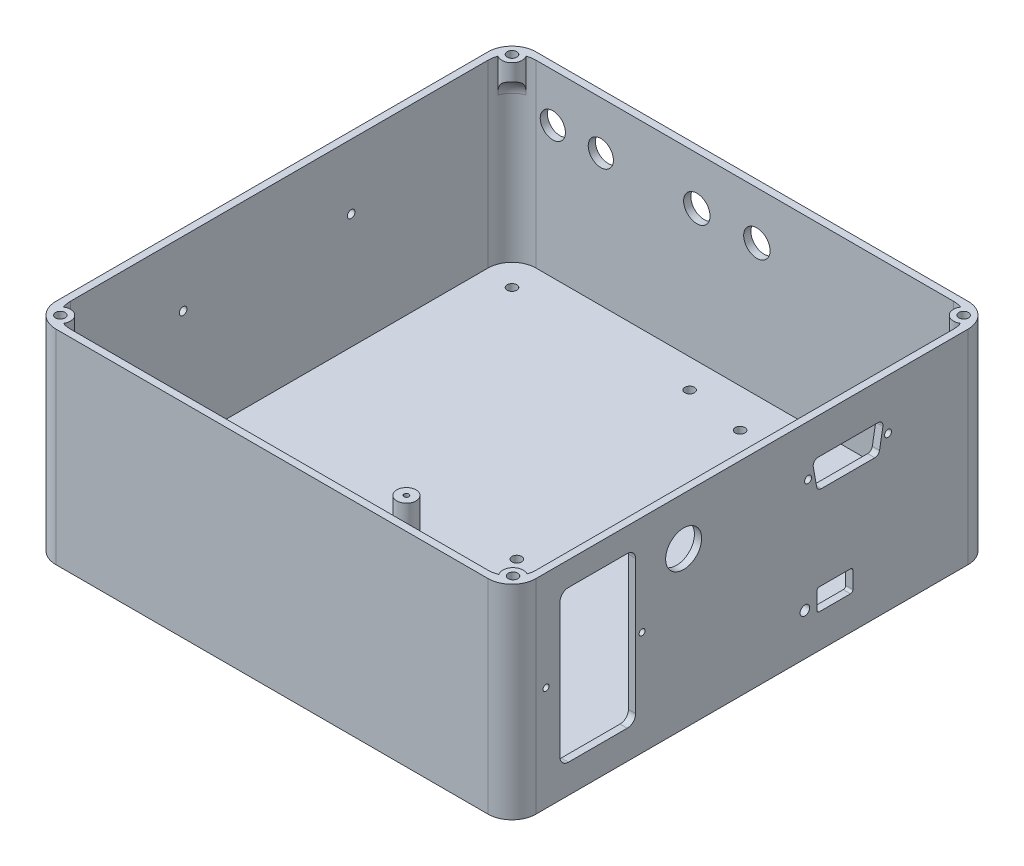
SolidWorks part; units mm, degrees
ref_plane "Front Plane" through (0, 0, 0) normal (0, 0, 1) x (1, 0, 0)
ref_plane "Top Plane" through (0, 0, 0) normal (0, 1, 0) x (1, 0, 0)
ref_plane "Right Plane" through (0, 0, 0) normal (1, 0, 0) x (0, 0, -1)
sketch "Sketch1" plane through (0, 0, 0) normal (0, 1, 0) x (1, 0, 0)
  line L1 (0, 0) -> (200, 0)
  line L2 (0, 0) -> (0, 200)
  line L3 (0, 200) -> (200, 200)
  line L4 (200, 0) -> (200, 200)
  dimension "D1" = 200
  dimension "D2" = 200
extrude "Boss-Extrude1" add sketch "Sketch1" along normal blind 4 and the other way blind 6
sketch "Sketch2" plane through (0, 4, 0) normal (0, 1, 0) x (1, 0, 0)
  line L1 (0, 0) -> (200, 0)
  line L2 (0, 0) -> (0, 200)
  line L3 (0, 200) -> (200, 200)
  line L4 (200, 0) -> (200, 200)
  line L5 (3, 3) -> (197, 3)
  line L6 (3, 3) -> (3, 197)
  line L7 (3, 197) -> (197, 197)
  line L8 (197, 3) -> (197, 197)
  dimension "D1" = 3
  dimension "D2" = 3
  dimension "D3" = 3
  dimension "D4" = 3
extrude "Boss-Extrude2" add sketch "Sketch2" along normal blind 75
sketch "Sketch3" plane through (200, 0, 0) normal (1, 0, 0) x (0, 0, -1)
  line L4 (200, 79) -> (200, -6) construction
  line L5 (156.65, 58.05) -> (123.35, 58.05) construction
  line L7 (0, 79) -> (200, 79) construction
  line L8 (140, 64) -> (140, 52.1) construction
  line L9 (127.5, 64) -> (152.5, 64)
  line L10 (126.9041, 53.6527) -> (125.4999, 61.6165)
  line L11 (151.126, 52) -> (128.8737, 52)
  line L12 (154.4999, 61.6165) -> (153.0957, 53.6527)
  circle A4 centre (156.65, 58.05) radius 1.45
  circle A5 centre (123.35, 58.05) radius 1.45
  arc A6 (153.0957, 53.6527) -> (151.126, 52) centre (151.126, 54) cw
  arc A7 (128.8737, 52) -> (126.9041, 53.6527) centre (128.8737, 54) cw
  arc A8 (152.5, 64) -> (154.4999, 61.6165) centre (152.4999, 61.9691) cw
  arc A9 (125.4999, 61.6165) -> (127.5, 64) centre (127.4999, 61.9691) cw
  point P0 (140, 58.05)
  point P15 (156.65, 58.05)
  point P16 (123.35, 58.05)
  point P21 (140, 58.05)
  dimension "D5" = 2.9
  dimension "D9" = 12
  dimension "D3" = 2
  dimension "D6" = 2.0309
  dimension "D7" = 2.0309
  dimension "D8" = 2
  dimension "D2" = 20
  dimension "D4" = 33.3
  dimension "D10" = 25
  dimension "D11" = 60
  dimension "D12" = 6.05
  dimension "D13" = 15
  dimension "D14" = 1.9696
  dimension "D15" = 22.2523
  dimension "D16" = 1.9696
  dimension "D18" = 2
  dimension "D19" = 2
  dimension "D20" = 2.0309
  dimension "D21" = 2.0309
  dimension "D22" = 2
  dimension "D23" = 2
extrude "Cut-Extrude1" cut sketch "Sketch3" against normal up to next
sketch "Sketch4" plane through (197, 0, 0) normal (1, 0, 0) x (0, 0, -1)
  line L0 (3, 4) -> (197, 4) construction
  line L1 (127, 8) -> (142, 8)
  line L2 (127, 8) -> (127, 17)
  line L3 (127, 17) -> (142, 17)
  line L4 (142, 8) -> (142, 17)
  line L5 (127, 17) -> (142, 8) construction
  line L6 (127, 8) -> (142, 17) construction
  line L8 (3, 4) -> (197, 4) construction
  line L10 (197, 79) -> (197, 4) construction
  circle A0 centre (122, 11.5) radius 2
  point P6 (134.5, 12.5)
  point P11 (100, 4)
  dimension "D4" = 12.5
  dimension "D5" = 4
  dimension "D6" = 7.5
  dimension "D1" = 15
  dimension "D2" = 4
  dimension "D3" = 9
  dimension "D7" = 55
extrude "Cut-Extrude2" cut sketch "Sketch4" along normal up to next
fillet "Fillet3" radius 1 4 edges at (198.5, 8, -127) (198.5, 17, -127) (198.5, 17, -142) (198.5, 8, -142)
fillet "Fillet1" radius 10 4 edges at (3, 41.5, -3) (197, 41.5, -3) (197, 41.5, -197) (3, 41.5, -197)
fillet "Fillet2" radius 10 4 edges at (0, 36.5, 0) (200, 36.5, 0) (200, 36.5, -200) (0, 36.5, -200)
sketch "Sketch5" plane through (0, 4, 0) normal (0, 1, 0) x (1, 0, 0)
  line L1 (114, 88) -> (190, 88)
  line L2 (114, 88) -> (114, 181)
  line L3 (114, 181) -> (190, 181)
  line L4 (190, 88) -> (190, 181)
  line L6 (187, 197) -> (13, 197) construction
  line L7 (197, 13) -> (197, 187) construction
  circle A0 centre (114, 88) radius 2
  circle A1 centre (114, 181) radius 2
  circle A2 centre (190, 181) radius 2
  circle A3 centre (190, 88) radius 2
  dimension "D5" = 4
  dimension "D1" = 16
  dimension "D2" = 7
  dimension "D3" = 93
  dimension "D4" = 76
extrude "Cut-Extrude3" cut sketch "Sketch5" against normal offset from surface (4 mm away) 6 contours A0 | A1 | A2 | A3 up to face at (100, -6, -100)
sketch "Sketch8" plane through (200, 0, -200) normal (-1, 0, 0) x (0, 0, 1)
  line L0 (148.5, 65.5) -> (148.5, 9.5)
  line L1 (149.5, 65.5) -> (149.5, 9.5)
  line L2 (152, 68) -> (176.5, 68)
  line L3 (179, 65.5) -> (179, 9.5)
  line L4 (152, 7) -> (176.5, 7)
  line L5 (152, 6) -> (176.5, 6)
  line L6 (180, 65.5) -> (180, 9.5)
  line L7 (152, 69) -> (176.5, 69)
  line L8 (149.5, 37.5) -> (189.1957, 37.5) construction
  line L9 (190, 79) -> (10, 79) construction
  line L10 (190, 79) -> (190, -6) construction
  arc A0 (149.5, 65.5) -> (152, 68) centre (152, 65.5) cw
  arc A1 (149.5, 9.5) -> (152, 7) centre (152, 9.5) ccw
  arc A2 (179, 9.5) -> (176.5, 7) centre (176.5, 9.5) cw
  arc A3 (176.5, 68) -> (179, 65.5) centre (176.5, 65.5) cw
  arc A4 (148.5, 9.5) -> (152, 6) centre (152, 9.5) ccw
  arc A5 (180, 9.5) -> (176.5, 6) centre (176.5, 9.5) cw
  arc A6 (176.5, 69) -> (180, 65.5) centre (176.5, 65.5) cw
  arc A7 (148.5, 65.5) -> (152, 69) centre (152, 65.5) cw
  circle A8 centre (185.8225, 37.5) radius 1.25
  circle A9 centre (145.8225, 37.5) radius 1.25
  point P7 (149.5, 68)
  point P10 (149.5, 7)
  point P15 (179, 68)
  dimension "D3" = 2.5
  dimension "D5" = 40
  dimension "D6" = 2.5
  dimension "D7" = 2.5
  dimension "D1" = 61
  dimension "D2" = 29.5
  dimension "D8" = 10
  dimension "D9" = 10
  dimension "D4" = 1
extrude "Cut-Extrude6" cut sketch "Sketch8" along normal up to surface (3 mm away) contours L7 A6 L6 A5 L5 A4 L0 A7 | A8 | A9 up to face at (197, 12.5, -134.5)
sketch "Sketch9" plane through (0, 0, -200) normal (0, 0, -1) x (-1, 0, 0)
  line L1 (-190, 79) -> (-10, 79) construction
  line L3 (-10, -6) -> (-10, 79) construction
  circle A0 centre (-105, 59) radius 5.5
  circle A1 centre (-80, 59) radius 5.5
  circle A2 centre (-20, 59) radius 5.25
  circle A3 centre (-40, 59) radius 5.25
  dimension "D1" = 11
  dimension "D3" = 20
  dimension "D4" = 10.5
  dimension "D5" = 20
  dimension "D7" = 20
  dimension "D8" = 70
  dimension "D2" = 25
  dimension "D6" = 10
extrude "Cut-Extrude7" cut sketch "Sketch9" against normal up to next
sketch "Sketch10" plane through (0, 0, -200) normal (0, 0, -1) x (-1, 0, 0)
  text T0 "shutter"
  text T1 "trigger"
  text T2 "GND"
  text T3 "-12V"
  text T4 "output"
extrude "Cut-Extrude8" cut sketch "Sketch10" against normal blind 0.5
sketch "Sketch11" plane through (0, 0, 0) normal (-1, 0, 0) x (0, 0, 1)
  line L0 (-190, -6) -> (-10, -6) construction
  line L1 (-190, 79) -> (-190, -6) construction
  circle A0 centre (-130, 52) radius 1.6
  circle A1 centre (-60, 52) radius 1.6
  dimension "D1" = 3.2
  dimension "D2" = 58
  dimension "D4" = 70
  dimension "D3" = 60
extrude "Cut-Extrude9" cut sketch "Sketch11" against normal up to next
sketch "Sketch13" plane through (0, 4, 0) normal (0, 1, 0) x (1, 0, 0)
  line L0 (13, 3) -> (187, 3) construction
  line L1 (3, 187) -> (3, 13) construction
  circle A0 centre (113, 43) radius 4
  dimension "D1" = 8
  dimension "D2" = 40
  dimension "D3" = 110
extrude "Boss-Extrude3" add sketch "Sketch13" along normal blind 45
sketch "Sketch14" plane through (0, 49, 0) normal (0, 1, 0) x (1, 0, 0)
  circle A0 centre (113, 43) radius 1
  dimension "D1" = 2
extrude "Cut-Extrude10" cut sketch "Sketch14" against normal blind 20
sketch "Sketch15" plane through (0, 79, 0) normal (0, 1, 0) x (1, 0, 0)
  circle A0 centre (5.9289, 5.9289) radius 4.2426
  arc A1 (3, 13) -> (13, 3) centre (13, 13) ccw construction
  circle A2 centre (5.9289, 194.0711) radius 4.2426
  arc A3 (13, 197) -> (3, 187) centre (13, 187) ccw construction
  circle A4 centre (194.0711, 194.0711) radius 4.2426
  arc A5 (197, 187) -> (187, 197) centre (187, 187) ccw construction
  circle A6 centre (194.2847, 6.1492) radius 4.2392
  arc A7 (187, 3) -> (197, 13) centre (187, 13) ccw construction
extrude "Boss-Extrude4" add sketch "Sketch15" against normal blind 6
fillet "Fillet4" radius 8 4 edges at (194.2847, 73, -6.1492) (5.9289, 73, -5.9289) (5.9289, 73, -194.0711) (194.0711, 73, -194.0711)
sketch "Sketch16" plane through (0, 79, 0) normal (0, 1, 0) x (1, 0, 0)
  circle A0 centre (194.2847, 6.1492) radius 2
  circle A1 centre (5.9289, 5.9289) radius 2
  circle A2 centre (5.9289, 194.0711) radius 2
  circle A3 centre (194.0711, 194.0711) radius 2
  dimension "D1" = 4
extrude "Cut-Extrude11" cut sketch "Sketch16" against normal blind 6
sketch "Sketch17" plane through (200, 0, 0) normal (1, 0, 0) x (0, 0, -1)
  line L0 (10, 79) -> (190, 79) construction
  line L1 (51.5, 65.5) -> (51.5, 9.5) construction
  circle A0 centre (71.5, 59) radius 7.5
  dimension "D1" = 15
  dimension "D2" = 20
  dimension "D3" = 20
extrude "Cut-Extrude12" cut sketch "Sketch17" against normal blind 10
sketch "Sketch19" plane through (0, 4, 0) normal (0, 1, 0) x (1, 0, 0)
  line L0 (10, 0) -> (190, 0) construction
  line L3 (0, 190) -> (0, 10) construction
  line L5 (190, 200) -> (10, 200) construction
  circle A0 centre (15, 185) radius 2
  circle A1 centre (89, 185) radius 2
  circle A2 centre (89, 15) radius 2
  circle A3 centre (15, 15) radius 2
  dimension "D6" = 4
  dimension "D7" = 4
  dimension "D8" = 4
  dimension "D9" = 4
  dimension "D1" = 74
  dimension "D2" = 170
  dimension "D3" = 74
  dimension "D4" = 15
  dimension "D5" = 15
  dimension "D10" = 15
  dimension "D11" = 170
extrude "Cut-Extrude13" cut sketch "Sketch19" against normal blind 6
